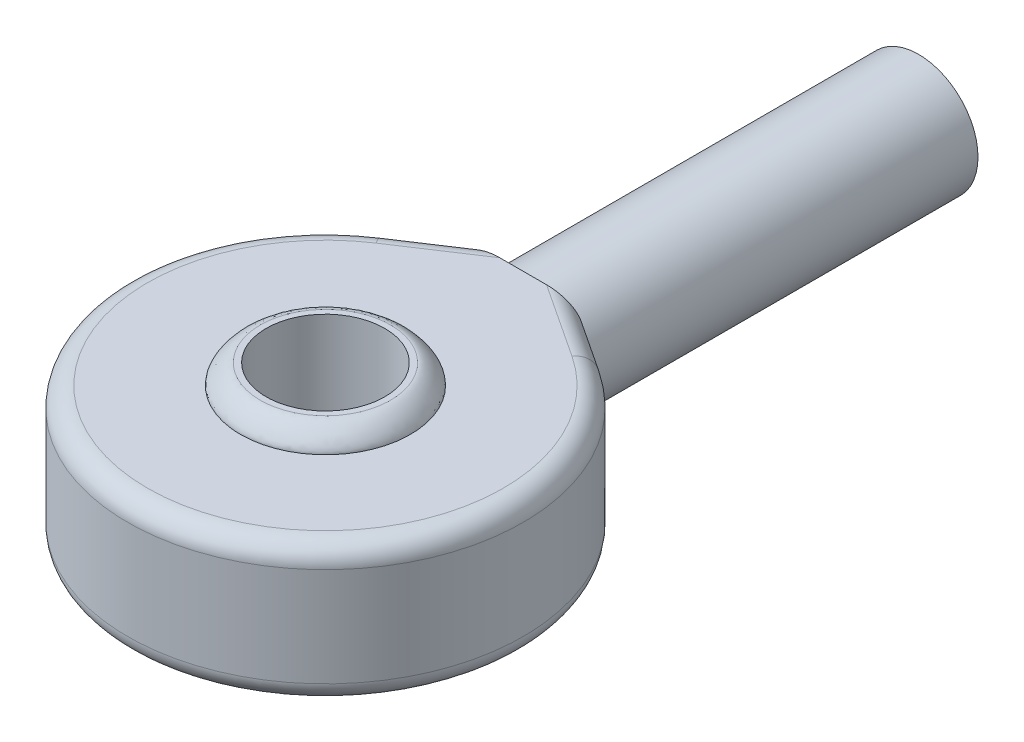
SolidWorks part; units mm, degrees
ref_plane "Alzado" through (0, 0, 0) normal (0, 0, 1) x (1, 0, 0)
ref_plane "Planta" through (0, 0, 0) normal (0, 1, 0) x (1, 0, 0)
ref_plane "Vista lateral" through (0, 0, 0) normal (1, 0, 0) x (0, 0, -1)
sketch "Croquis1" plane through (0, 0, 0) normal (0, 0, 1) x (1, 0, 0)
  circle A0 centre (0, 0) radius 3
  dimension "D1" = 6
extrude "Saliente-Extruir1" add sketch "Croquis1" along normal blind 20
sketch "Croquis2" plane through (0, 0, 0) normal (0, 1, 0) x (1, 0, 0)
  line L0 (0, -20) -> (0, -40) construction
  line L1 (-3, -20) -> (3, -20) construction
  line L2 (-5.5046, -21.6514) -> (-3, -20)
  line L3 (-3, -20) -> (3, -20)
  line L5 (3, -20) -> (5.5046, -21.6514)
  arc A0 (-5.5046, -21.6514) -> (5.5046, -21.6514) centre (0, -30) ccw
  circle A1 centre (0, -30) radius 3
  dimension "D2" = 6
  dimension "D3" = 10
  dimension "D1" = 20
extrude "Saliente-Extruir2" add sketch "Croquis2" along normal mid plane 7
fillet "Redondeo2" radius 1 6 edges at (-4.2523, 3.5, 20.8257) (0, 3.5, 40) (-4.2523, -3.5, 20.8257) (0, -3.5, 40) (4.2523, 3.5, 20.8257) (4.2523, -3.5, 20.8257)
sketch "Croquis3" plane through (0, 0, 0) normal (0, 1, 0) x (1, 0, 0)
  circle A0 centre (0, -30) radius 4.2966
  circle A1 centre (0, -30) radius 3 construction
  circle A2 centre (0, -30) radius 3
extrude "Saliente-Extruir3" add sketch "Croquis3" along normal mid plane 9
fillet "Redondeo3" radius 1 2 edges at (0, -4.5, 34.2966) (0, 4.5, 34.2966) conic radius 2
